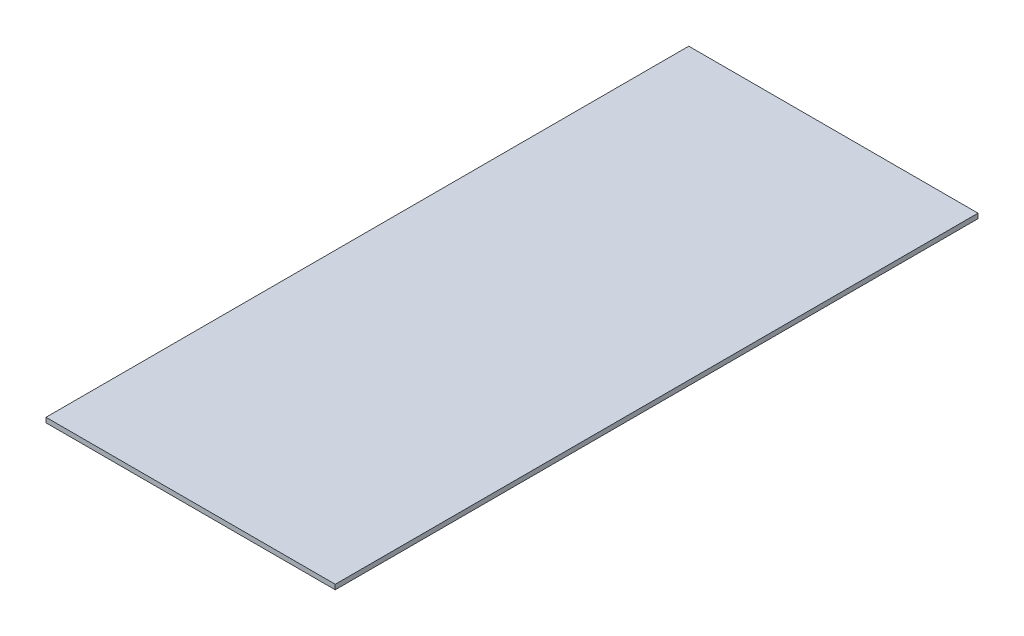
SolidWorks part; units mm, degrees
ref_plane "Front Plane" through (0, 0, 0) normal (0, 0, 1) x (1, 0, 0)
ref_plane "Top Plane" through (0, 0, 0) normal (0, 1, 0) x (1, 0, 0)
ref_plane "Right Plane" through (0, 0, 0) normal (1, 0, 0) x (0, 0, -1)
sketch "Sketch1" plane through (0, 0, 0) normal (0, 1, 0) x (1, 0, 0)
  line L1 (0, 0) -> (180, 0)
  line L2 (0, 0) -> (0, 400)
  line L3 (0, 400) -> (180, 400)
  line L4 (180, 0) -> (180, 400)
  dimension "D1" = 400
  dimension "D2" = 180
extrude "Boss-Extrude1" add sketch "Sketch1" along normal blind 3
